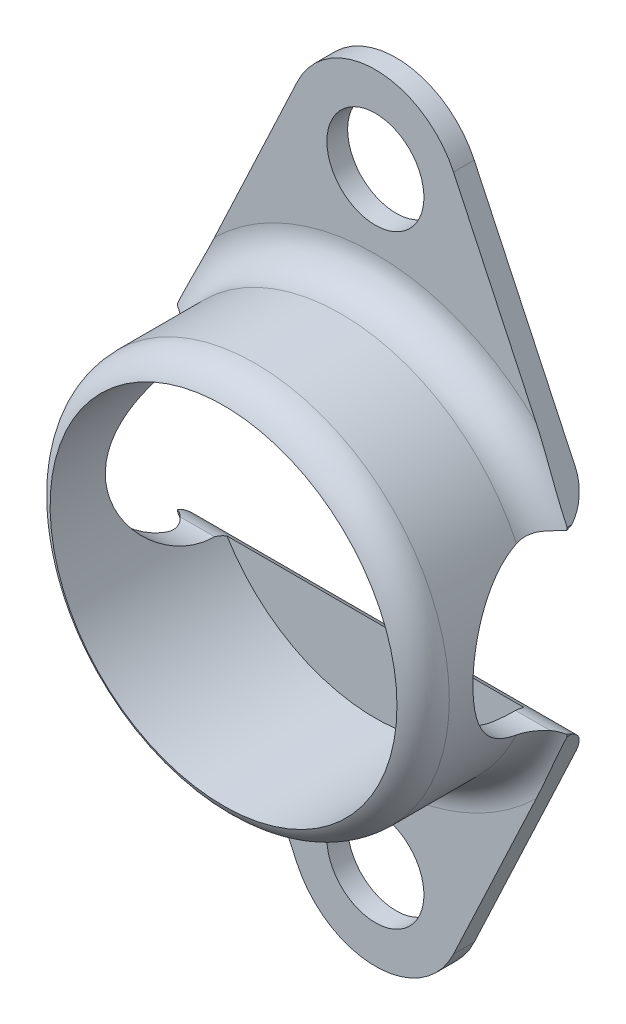
SolidWorks part; units mm, degrees
material "Galvanized Steel"
ref_plane "Front Plane" through (0, 0, 0) normal (0, 0, 1) x (1, 0, 0)
ref_plane "Top Plane" through (0, 0, 0) normal (0, 1, 0) x (1, 0, 0)
ref_plane "Right Plane" through (0, 0, 0) normal (1, 0, 0) x (0, 0, -1)
sketch "Sketch1" plane through (0, 0, 0) normal (0, 0, 1) x (1, 0, 0)
  line L2 (-14.3256, -15.5575) -> (-14.3256, -28.8925)
  line L3 (14.3256, -15.5575) -> (14.3256, -28.8925)
  line L4 (14.3256, -28.8925) -> (5.7472, -47.1503)
  line L6 (-14.3256, -28.8925) -> (-5.7472, -47.1503)
  line L8 (-14.3256, -15.5575) -> (-5.751, 2.6924)
  line L9 (14.3256, -15.5575) -> (5.751, 2.6924)
  circle A3 centre (0, 0) radius 3.5687
  circle A4 centre (0, -44.45) radius 3.5687
  arc A6 (-5.7472, -47.1503) -> (5.7472, -47.1503) centre (0, -44.45) ccw
  arc A7 (5.751, 2.6924) -> (-5.751, 2.6924) centre (0, 0) ccw
  point P19 (-14.3256, -22.225)
  dimension "D2" = 44.45
  dimension "D7" = 12.7
  dimension "D6" = 3.6576
  dimension "D9" = 7.1374
  dimension "D10" = 7.1374
  dimension "D3" = 12.7
  dimension "D4" = 28.6512
  dimension "D5" = 13.335
  dimension "D8" = 22.225
extrude "Boss-Extrude1" add sketch "Sketch1" along normal mid plane 1.524
sketch "Sketch3" plane through (0, 0, 0.762) normal (0, 0, 1) x (1, 0, 0)
  circle A0 centre (0, -22.225) radius 14.2875
  circle A1 centre (0, -22.225) radius 12.7635
  dimension "D1" = 28.575
  dimension "D3" = 1.524
  dimension "D2" = 22.225
extrude "Boss-Extrude2" add sketch "Sketch3" along normal blind 11.176
fillet "Fillet4" radius 2.54 1 edges at (14.2875, -22.225, 11.938)
fillet "Fillet7" radius 2.54 1 edges at (14.2875, -22.225, 0.762)
sketch "Sketch4" plane through (14.3256, 0, 0) normal (1, 0, 0) x (0, 0, -1)
  line L0 (0.762, -15.5575) -> (0.762, 2.6924) construction
  line L1 (0.762, -47.1503) -> (0.762, -28.8925) construction
  line L2 (0.762, -13.1814) -> (0.762, -31.2144)
  arc A0 (-1.524, -15.875) -> (-1.524, -28.575) centre (-1.524, -22.225) ccw
  arc A1 (-1.524, -15.875) -> (0.762, -13.1814) centre (-2.0315, -13.1275) ccw
  arc A2 (-1.524, -28.575) -> (0.762, -31.2144) centre (-2.0299, -31.3228) cw
  dimension "D1" = 12.7
  dimension "D5" = 2.794
  dimension "D6" = 2.794
  dimension "D2" = 8.636
  dimension "D3" = 22.225
  dimension "D4" = 18.0329
extrude "Cut-Extrude1" cut sketch "Sketch4" against normal through all
